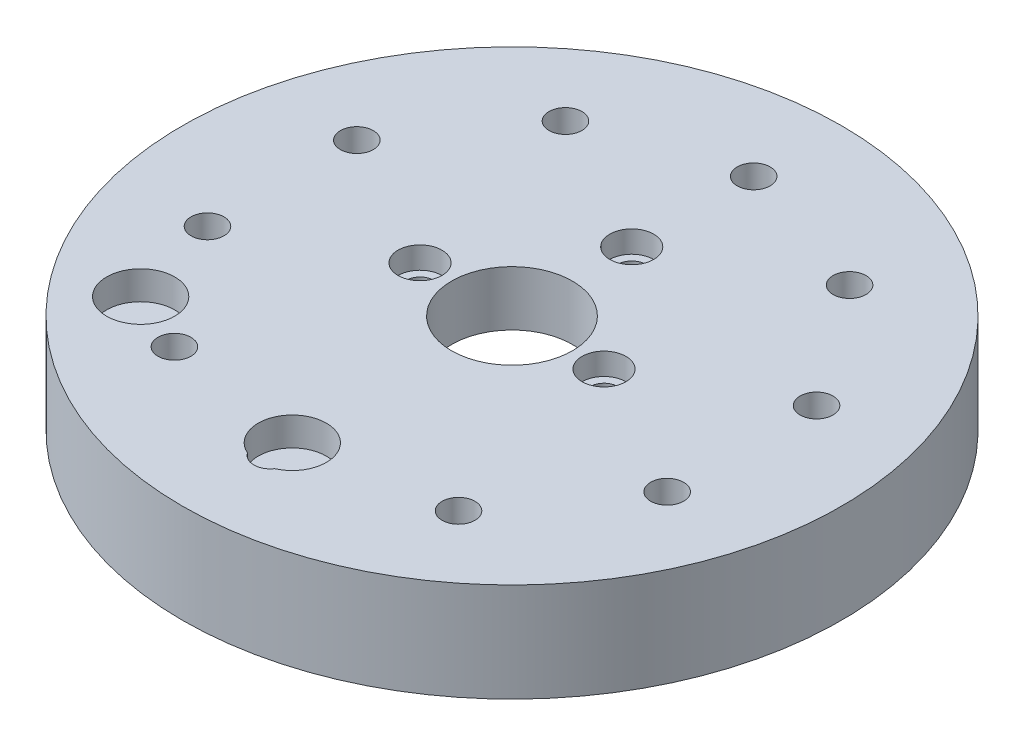
SolidWorks part; units mm, degrees
ref_plane "前视基准面" through (0, 0, 0) normal (0, 0, 1) x (1, 0, 0)
ref_plane "上视基准面" through (0, 0, 0) normal (0, 1, 0) x (1, 0, 0)
ref_plane "右视基准面" through (0, 0, 0) normal (1, 0, 0) x (0, 0, -1)
other "Configuration Table"
sketch "草图1" plane through (0, 0, 0) normal (0, 1, 0) x (1, 0, 0)
  circle A0 centre (0, 0) radius 30
  circle A1 centre (-8.375, 0) radius 1.25
  circle A2 centre (-8.375, 0) radius 2
  circle A3 centre (8.375, 0) radius 1.25
  circle A4 centre (8.375, 0) radius 2
  circle A11 centre (0, 10.9) radius 1.25
  circle A12 centre (0, 10.9) radius 2
  circle A16 centre (0, 0) radius 5.5
  point P0 (0, 0)
  dimension "D1" = 2.5
  dimension "D2" = 4
  dimension "D3" = 11
  dimension "D4" = 60
extrude "凸台-拉伸1" add sketch "草图1" along normal blind 5 contours A0 | A16 | A1 | A11 | A3
extrude "切除-拉伸2" cut sketch "草图1<15>" against normal blind 2 from surface contours A2 | A4 | A12 starting at face at (0, 5, -9.65)
sketch "草图1<15>" plane through (0, 0, 0) normal (0, 1, 0) x (1, 0, 0) same geometry as "草图1"
sketch "草图2" plane through (0, 5, 0) normal (0, 1, 0) x (1, 0, 0)
  circle A0 centre (0, -20) radius 3.1
  circle A1 centre (-18.4285, -15.375) radius 3.1
  dimension "D1" = 6.2
  dimension "D2" = 20
  dimension "D3" = 19
  dimension "D4" = 24
extrude "切除-拉伸3" cut sketch "草图2" against normal blind 2.6 contours A0 | A1
sketch "草图3" plane through (0, 0, 0) normal (0, -1, 0) x (1, 0, 0)
  circle A0 centre (0, 0) radius 14
  circle A1 centre (0, 0) radius 30
  circle A2 centre (0, 0) radius 30 construction
  dimension "D1" = 28
extrude "凸台-拉伸2" add sketch "草图3" along normal blind 4 contours A1 | A0
sketch "草图4" plane through (0, -4, 0) normal (0, -1, 0) x (1, 0, 0)
  circle A0 centre (0, -22) radius 2.25
  circle A1 centre (0, -22) radius 1.5
  dimension "D1" = 3
  dimension "D2" = 4.5
  dimension "D3" = 22
extrude "切除-拉伸4" cut sketch "草图4" against normal through all contours A1
extrude "切除-拉伸5" cut sketch "草图4<3>" against normal offset from surface (6 mm away) 3 contours A0 up to face at (0, 5, -23.5)
sketch "草图4<3>" plane through (0, -4, 0) normal (0, -1, 0) x (1, 0, 0) same geometry as "草图4"
pattern_circular "阵列(圆周)1" count 10 over 360 about axis through (0, 5, 0) along (0, -1, 0) of "切除-拉伸4", "切除-拉伸5"
